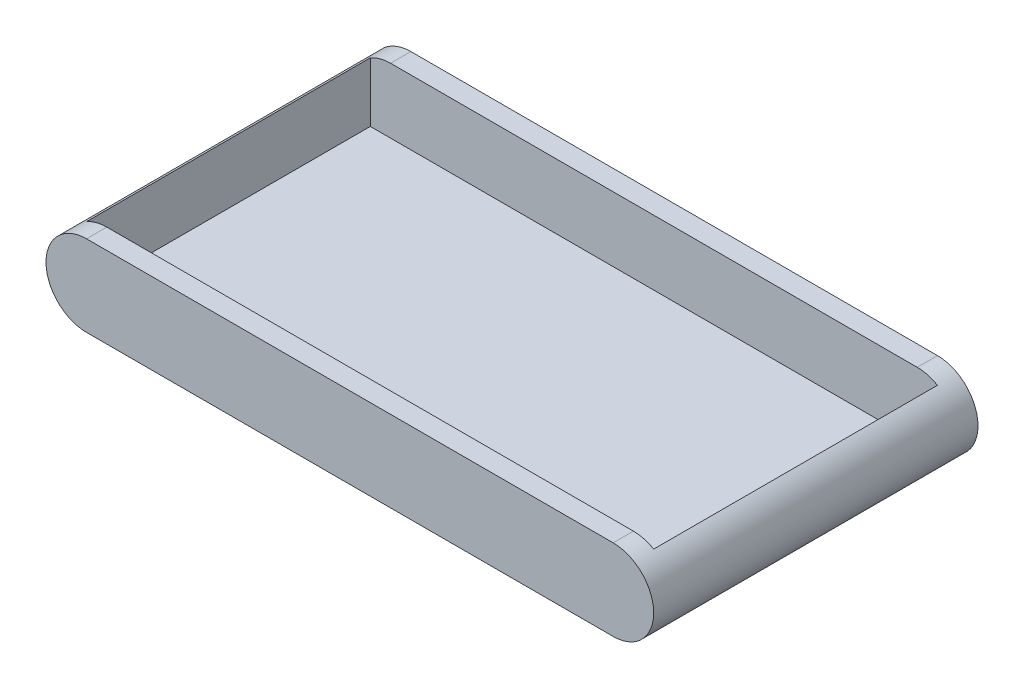
SolidWorks part; units mm, degrees
ref_plane "Front Plane" through (0, 0, 0) normal (0, 0, 1) x (1, 0, 0)
ref_plane "Top Plane" through (0, 0, 0) normal (0, 1, 0) x (1, 0, 0)
ref_plane "Right Plane" through (0, 0, 0) normal (1, 0, 0) x (0, 0, -1)
sketch "Sketch1" plane through (0, 0, 0) normal (0, 0, 1) x (1, 0, 0)
  line L0 (-3.9005, 10.8865) -> (126.0033, 10.8865)
  line L1 (-3.9005, -9.1135) -> (126.0033, -9.1135)
  arc A0 (126.0033, -9.1135) -> (126.0033, 10.8865) centre (126.0033, 0.8865) ccw
  arc A1 (-3.9005, 10.8865) -> (-3.9005, -9.1135) centre (-3.9005, 0.8865) ccw
extrude "Boss-Extrude1" add sketch "Sketch1" against normal blind 80
sketch "Sketch2" plane through (0, 10.8865, 0) normal (0, 1, 0) x (1, 0, 0)
  line L0 (-8.9005, 75) -> (-8.9005, 5)
  line L1 (-13.9005, 80) -> (136.0033, 80) construction
  line L2 (-13.9005, 80) -> (-13.9005, 0) construction
  line L3 (-13.9005, 0) -> (136.0033, 0) construction
  line L4 (136.0033, 80) -> (136.0033, 0) construction
  line L5 (-8.9005, 5) -> (131.0033, 5)
  line L6 (131.0033, 75) -> (131.0033, 5)
  line L7 (-8.9005, 75) -> (131.0033, 75)
  dimension "D1" = 5
extrude "Cut-Extrude1" cut sketch "Sketch2" against normal blind 16 contours L7 L6 L5 L0
